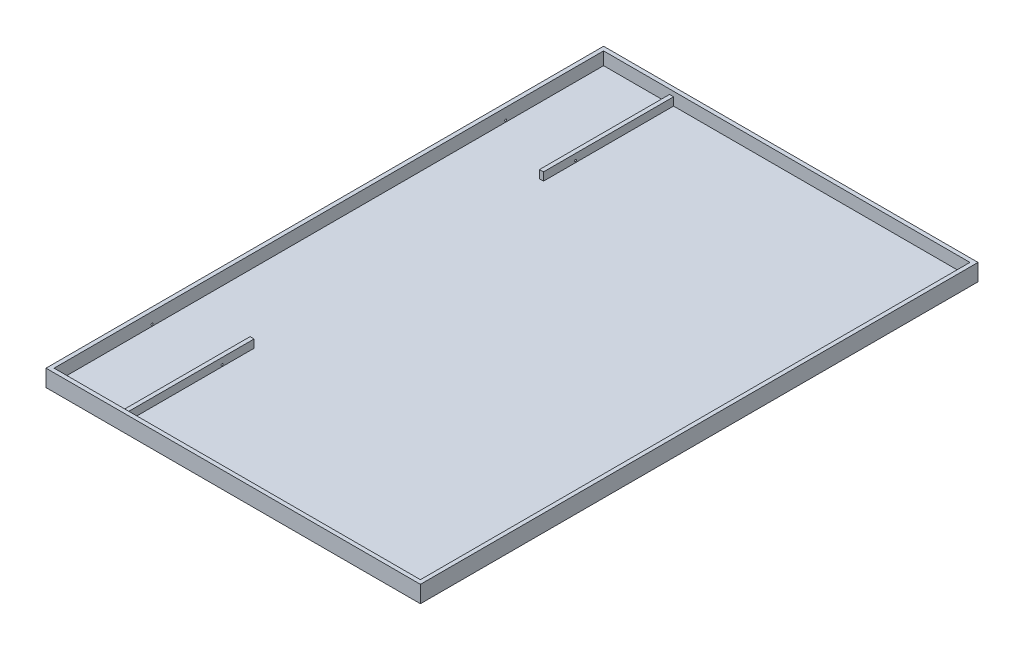
SolidWorks part; units mm, degrees
ref_plane "Plan de face" through (0, 0, 0) normal (0, 0, 1) x (1, 0, 0)
ref_plane "Plan de dessus" through (0, 0, 0) normal (0, 1, 0) x (1, 0, 0)
ref_plane "Plan de droite" through (0, 0, 0) normal (1, 0, 0) x (0, 0, -1)
sketch "Esquisse1" plane through (0, 0, 0) normal (0, 1, 0) x (1, 0, 0)
  line L0 (-1000, 1500) -> (1000, -1500) construction
  line L1 (-1000, 1500) -> (1000, 1500)
  line L2 (-1000, 1500) -> (-1000, -1500)
  line L3 (-1000, -1500) -> (1000, -1500)
  line L4 (1000, 1500) -> (1000, -1500)
  dimension "D1" = 3000
  dimension "D2" = 2000
extrude "Boss.-Extru.1" add sketch "Esquisse1" against normal blind 22
sketch "Esquisse2" plane through (0, 0, 0) normal (0, 1, 0) x (1, 0, 0)
  line L0 (-1022, 1522) -> (-1022, -1522)
  line L1 (-1022, -1522) -> (1022, -1522)
  line L2 (1022, -1522) -> (1022, 1522)
  line L3 (1022, 1522) -> (-1022, 1522)
  line L4 (-1000, 1500) -> (-1000, -1500)
  line L5 (-1000, -1500) -> (1000, -1500)
  line L6 (1000, -1500) -> (1000, 1500)
  line L7 (1000, 1500) -> (-1000, 1500)
  line L8 (-1000, 1500) -> (-1000, -1500)
  line L9 (-1000, -1500) -> (1000, -1500)
  line L10 (1000, -1500) -> (1000, 1500)
  line L11 (1000, 1500) -> (-1000, 1500)
  dimension "D1" = 0
  dimension "D2" = 22
extrude "Boss.-Extru.2" add sketch "Esquisse2" along normal blind 70 and the other way up to surface (22 mm away) other way up to face at (0, -22, 0)
sketch "Esquisse3" plane through (0, 0, 0) normal (0, 1, 0) x (1, 0, 0)
  line L0 (1000, 1500) -> (-1000, 1500) construction
  line L1 (-640, 1500) -> (-618, 1500)
  line L2 (-640, 1500) -> (-640, 790)
  line L3 (-640, 790) -> (-618, 790)
  line L4 (-618, 1500) -> (-618, 790)
  line L5 (-1000, 1500) -> (-1000, -1500) construction
  dimension "D1" = 22
  dimension "D2" = 710
  dimension "D3" = 360
extrude "Boss.-Extru.3" add sketch "Esquisse3" along normal blind 44
sketch "Esquisse4" plane through (-618, 0, 0) normal (1, 0, 0) x (0, 0, -1)
  line L0 (1500, 0) -> (1500, 70) construction
  line L1 (1500, 0) -> (-1500, 0) construction
  circle A0 centre (965, 10) radius 5
  dimension "D3" = 10
  dimension "D1" = 535
  dimension "D2" = 10
extrude "Enlèv. mat.-Extru.1" cut sketch "Esquisse4" against normal through all
mirror "Symétrie1" about plane through (0, 0, 0) normal (0, 0, 1) of "Enlèv. mat.-Extru.1", "Boss.-Extru.3"
